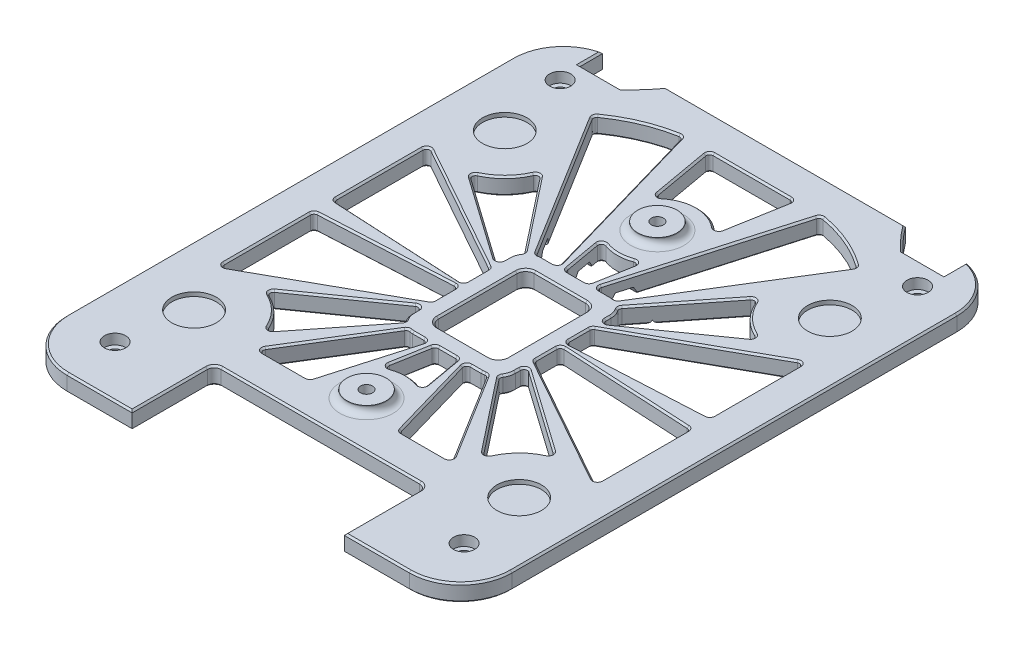
SolidWorks part; units mm, degrees
ref_plane "Front Plane" through (0, 0, 0) normal (0, 0, 1) x (1, 0, 0)
ref_plane "Top Plane" through (0, 0, 0) normal (0, 1, 0) x (1, 0, 0)
ref_plane "Right Plane" through (0, 0, 0) normal (1, 0, 0) x (0, 0, -1)
sketch "Sketch1" plane through (0, 0, 0) normal (0, 1, 0) x (1, 0, 0)
  line L0 (65, 160) -> (65, 24) construction
  line L5 (96, 0) -> (96, 22)
  line L7 (11.8, 153.04) -> (23.8, 153.04)
  line L9 (11.8, 153.04) -> (11.8, 159.6547)
  line L10 (118.2, 153.04) -> (106.2, 153.04)
  line L11 (118.2, 153.04) -> (118.2, 159.6547)
  line L18 (18, 160) -> (18, 155.5)
  line L19 (16.5, 154) -> (12.5, 154)
  line L20 (11, 155.5) -> (11, 159.4568)
  line L21 (0, 145) -> (0, 15)
  line L22 (15, 0) -> (34, 0)
  line L23 (34, 0) -> (34, 22.5)
  line L24 (35.5, 24) -> (90.5, 24)
  line L25 (96, 18.5) -> (96, 0)
  line L26 (96, 0) -> (115, 0)
  line L27 (130, 15) -> (130, 145)
  line L28 (119, 159.4568) -> (119, 155.5)
  line L29 (117.5, 154) -> (113.5, 154)
  line L30 (112, 155.5) -> (112, 160)
  line L31 (112, 160) -> (18, 160)
  line L35 (0, 145) -> (0, 15)
  line L36 (15, 0) -> (34, 0)
  line L37 (34, 0) -> (34, 22)
  line L38 (36, 24) -> (94, 24)
  line L40 (96, 0) -> (115, 0)
  line L41 (130, 15) -> (130, 145)
  line L45 (100, 160) -> (30, 160)
  circle A6 centre (116, 15) radius 1.75
  circle A7 centre (14, 15) radius 1.75
  circle A8 centre (65, 37.5) radius 1.75
  arc A10 (16.5, 154) -> (18, 155.5) centre (16.5, 155.5) ccw
  arc A11 (11, 155.5) -> (12.5, 154) centre (12.5, 155.5) ccw
  arc A12 (11, 159.4568) -> (0, 145) centre (15, 145) ccw
  arc A13 (0, 15) -> (15, 0) centre (15, 15) ccw
  arc A14 (35.5, 24) -> (34, 22.5) centre (35.5, 22.5) ccw
  arc A15 (96, 18.5) -> (90.5, 24) centre (90.5, 18.5) ccw
  arc A16 (115, 0) -> (130, 15) centre (115, 15) ccw
  arc A17 (130, 145) -> (119, 159.4568) centre (115, 145) ccw
  arc A18 (117.5, 154) -> (119, 155.5) centre (117.5, 155.5) ccw
  arc A19 (112, 155.5) -> (113.5, 154) centre (113.5, 155.5) ccw
  arc A22 (11, 159.4568) -> (0, 145) centre (15, 145) ccw
  arc A23 (0, 15) -> (15, 0) centre (15, 15) ccw
  arc A26 (115, 0) -> (130, 15) centre (115, 15) ccw
  arc A27 (130, 145) -> (119, 159.4568) centre (115, 145) ccw
  circle A30 centre (65, 122.5) radius 1.75
  circle A31 centre (12.78, 146.3) radius 1.75
  circle A32 centre (117.22, 146.3) radius 1.75
  arc A33 (36, 24) -> (34, 22) centre (36, 22) ccw
  arc A34 (94, 24) -> (96, 22) centre (94, 22) cw
  arc A35 (11, 159.4568) -> (11.8, 159.6547) centre (15, 145) cw
  arc A36 (23.8, 153.04) -> (30, 160) centre (-10.2724, 189.6333) ccw
  arc A37 (106.2, 153.04) -> (100, 160) centre (140.2724, 189.6333) cw
  arc A38 (119, 159.4568) -> (118.2, 159.6547) centre (115, 145) ccw
  dimension "D4" = 3.5
  dimension "D5" = 4
  dimension "D8" = 50
  dimension "D11" = 37.5
  dimension "D12" = 37.5
  dimension "D13" = 3.5
  dimension "D14" = 3.5
  dimension "D19" = 3.5
  dimension "D20" = 3.5
  dimension "D21" = 3.5
  dimension "D2" = 13.7
  dimension "D3" = 12.78
  dimension "D6" = 11.8
  dimension "D7" = 6.74
  dimension "D9" = 12
  dimension "D10" = 35
  dimension "D15" = 15
  dimension "D16" = 15
  dimension "D17" = 102
  dimension "D18" = 51
  dimension "D1" = 0
extrude "Boss-Extrude1" add sketch "Sketch1" along normal blind 5
chamfer "Chamfer1" distance 3.55 angle 45 2 edges at (65, 0, -35.75) (65, 0, -120.75)
sketch "Sketch2" plane through (0, 5, 0) normal (0, 1, 0) x (1, 0, 0)
  line L26 (15, 145) -> (15, 15)
  line L27 (15, 138.04) -> (15, 39) construction
  line L29 (100, 145) -> (36.9808, 145)
  line L30 (93.0192, 145) -> (36.9808, 145) construction
  line L40 (29.264, 138.04) -> (11.8, 138.04)
  line L41 (118.2, 138.04) -> (100.736, 138.04)
  line L42 (115, 138.04) -> (100.736, 138.04) construction
  line L43 (29.264, 138.04) -> (15, 138.04) construction
  line L45 (115, 15) -> (115, 145)
  line L46 (115, 39) -> (115, 138.04) construction
  line L48 (94, 39) -> (36, 39)
  line L49 (115, 39) -> (15, 39) construction
  circle A2 centre (65, 122.5) radius 11.75
  circle A3 centre (65, 122.5) radius 11.75 construction
  circle A5 centre (65, 37.5) radius 11.75
  circle A6 centre (65, 37.5) radius 11.75 construction
  arc A22 (34.0217, 142.062) -> (36.9808, 145) centre (-10.2724, 189.6333) ccw
  arc A28 (87.9183, 151.11) -> (100.736, 138.04) centre (140.2724, 189.6333) ccw
  arc A29 (93.0192, 145) -> (100.736, 138.04) centre (140.2724, 189.6333) ccw construction
  arc A30 (29.264, 138.04) -> (42.0817, 151.11) centre (-10.2724, 189.6333) ccw
  arc A31 (29.264, 138.04) -> (36.9808, 145) centre (-10.2724, 189.6333) ccw construction
  arc A33 (93.0192, 145) -> (76.6539, 39) centre (166.3728, 79.4116) ccw
  arc A34 (36.9808, 145) -> (53.3461, 39) centre (-36.3728, 79.4116) cw
  arc A35 (111, 22) -> (94, 39) centre (94, 22) ccw
  arc A36 (36, 39) -> (19, 22) centre (36, 22) ccw
  arc A41 (36.9808, 145) -> (53.3461, 39) centre (78.1854, 97.0983) ccw
  arc A42 (93.0192, 145) -> (76.6539, 39) centre (51.8146, 97.0983) cw
  dimension "D1" = 10
  dimension "D2" = 10
  dimension "D3" = 15
  dimension "D4" = 15
  dimension "D5" = 15
  dimension "D6" = 15
  dimension "D7" = 15
  dimension "D8" = 15
extrude "Cut-Extrude1" [suppressed] cut sketch "Sketch2" against normal up to next
sketch "Sketch5" plane through (0, 5, 0) normal (0, 1, 0) x (1, 0, 0)
  line L0 (65, 24) -> (65, 160) construction
  line L1 (36, 24) -> (94, 24) construction
  line L2 (100, 160) -> (30, 160) construction
  line L3 (0, 80) -> (130, 80) construction
  line L4 (0, 145) -> (0, 15) construction
  line L5 (130, 15) -> (130, 145) construction
  circle A0 centre (17.5, 34.6) radius 6.5
  circle A1 centre (65, 37.5) radius 1.75 construction
  circle A2 centre (65, 122.5) radius 1.75 construction
  circle A3 centre (17.5, 125.4) radius 6.5
  circle A4 centre (112.5, 34.6) radius 6.5
  circle A5 centre (112.5, 125.4) radius 6.5
  dimension "D1" = 13
  dimension "D3" = 2.9
  dimension "D4" = 42.5
  dimension "D2" = 47.5
extrude "Cut-Extrude3" cut sketch "Sketch5" against normal blind 1.2
sketch "Sketch6" plane through (0, 5, 0) normal (0, 1, 0) x (1, 0, 0)
  line L0 (130, 15) -> (130, 145) construction
  line L1 (0, 80) -> (130, 80) construction
  line L2 (0, 145) -> (0, 15) construction
  line L3 (50, 99) -> (50, 61) construction
  line L4 (50, 61) -> (80, 61) construction
  line L5 (80, 99) -> (80, 61) construction
  line L6 (50, 99) -> (80, 99) construction
  line L7 (65, 80) -> (104.0126, 143.04) construction
  line L8 (65, 80) -> (96.8102, 120.293) construction
  line L9 (65, 80) -> (120, 110.7031) construction
  line L10 (65, 80) -> (107.2351, 109.7625) construction
  line L11 (65, 80) -> (85.1379, 150) construction
  line L12 (65, 80) -> (77.4055, 150) construction
  line L13 (65, 80) -> (120, 82.8824) construction
  line L14 (61.6328, 99) -> (68.3672, 99)
  line L15 (68.3672, 99) -> (70.7122, 112.2319)
  line L16 (77.4055, 150) -> (73.8929, 130.1798)
  line L17 (77.4055, 150) -> (52.5945, 150)
  line L23 (70.466, 99) -> (85.1379, 150)
  line L24 (65, 160) -> (65, 24) construction
  line L29 (100, 160) -> (30, 160) construction
  line L30 (36, 24) -> (94, 24) construction
  line L32 (55, 94) -> (75, 94) construction
  line L33 (55, 94) -> (55, 66) construction
  line L34 (55, 66) -> (75, 66) construction
  line L35 (75, 94) -> (75, 66) construction
  line L36 (10, 143.04) -> (10, 15)
  line L37 (15, 10) -> (24, 10)
  line L38 (24, 10) -> (24, 22)
  line L39 (36, 34) -> (94, 34)
  line L40 (106, 22) -> (106, 10)
  line L41 (106, 10) -> (115, 10)
  line L42 (120, 15) -> (120, 143.04)
  line L43 (120, 143.04) -> (102.4695, 143.04)
  line L44 (95.2258, 150) -> (34.7742, 150)
  line L45 (27.5305, 143.04) -> (10, 143.04)
  line L46 (10, 143.04) -> (10, 15) construction
  line L47 (15, 10) -> (24, 10) construction
  line L48 (24, 10) -> (24, 22) construction
  line L49 (36, 34) -> (94, 34) construction
  line L50 (106, 22) -> (106, 10) construction
  line L51 (106, 10) -> (115, 10) construction
  line L52 (120, 15) -> (120, 143.04) construction
  line L53 (120, 143.04) -> (102.4695, 143.04) construction
  line L54 (95.2258, 150) -> (34.7742, 150) construction
  line L55 (27.5305, 143.04) -> (10, 143.04) construction
  line L57 (80, 90.5703) -> (107.2351, 109.7625)
  line L58 (120, 110.7031) -> (120, 82.8824)
  line L59 (120, 82.8824) -> (80, 80.7861)
  line L60 (80, 80.7861) -> (80, 88.3736)
  line L61 (80, 88.3736) -> (120, 110.7031)
  line L64 (57.5, 94) -> (72.5, 94)
  line L65 (75, 68.5) -> (75, 91.5)
  line L66 (80, 90.5703) -> (80, 94)
  line L67 (96.8102, 120.293) -> (78.7041, 97.3585)
  line L68 (103.5218, 142.247) -> (76.5963, 98.7383)
  line L69 (70.466, 99) -> (75, 99)
  line L70 (57.5, 66) -> (72.5, 66)
  line L71 (80, 79.2139) -> (80, 71.6264)
  line L72 (120, 77.1176) -> (80, 79.2139)
  line L73 (120, 49.2969) -> (120, 77.1176)
  line L74 (80, 71.6264) -> (120, 49.2969)
  line L75 (96.8102, 39.707) -> (78.7041, 62.6415)
  line L76 (80, 69.4297) -> (107.2351, 50.2375)
  line L77 (80, 69.4297) -> (80, 66)
  line L78 (70.466, 61) -> (85.1379, 10) construction
  line L79 (70.466, 61) -> (75, 61)
  line L80 (103.5218, 17.753) -> (76.5963, 61.2617) construction
  line L81 (68.3672, 61) -> (70.7122, 47.7681)
  line L82 (61.6328, 61) -> (68.3672, 61)
  line L87 (78.2335, 34) -> (94, 34)
  line L88 (94, 34) -> (93.4673, 34)
  line L89 (70.466, 61) -> (78.2335, 34)
  line L90 (76.5963, 61.2617) -> (93.4673, 34)
  line L91 (61.6328, 61) -> (59.2878, 47.7681)
  line L92 (59.534, 61) -> (55, 61)
  line L93 (59.534, 61) -> (51.7665, 34)
  line L94 (51.7665, 34) -> (36, 34)
  line L95 (36, 34) -> (36.5327, 34)
  line L96 (53.4037, 61.2617) -> (36.5327, 34)
  line L97 (50, 69.4297) -> (22.7649, 50.2375)
  line L98 (50, 69.4297) -> (50, 66)
  line L99 (33.1898, 39.707) -> (51.2959, 62.6415)
  line L100 (10, 77.1176) -> (50, 79.2139)
  line L101 (10, 49.2969) -> (10, 77.1176)
  line L102 (50, 71.6264) -> (10, 49.2969)
  line L103 (50, 79.2139) -> (50, 71.6264)
  line L104 (50, 80.7861) -> (50, 88.3736)
  line L105 (10, 82.8824) -> (50, 80.7861)
  line L106 (10, 110.7031) -> (10, 82.8824)
  line L107 (50, 88.3736) -> (10, 110.7031)
  line L108 (33.1898, 120.293) -> (51.2959, 97.3585)
  line L109 (50, 90.5703) -> (22.7649, 109.7625)
  line L110 (50, 90.5703) -> (50, 94)
  line L111 (59.534, 99) -> (44.8621, 150)
  line L112 (59.534, 99) -> (55, 99)
  line L113 (26.4782, 142.247) -> (53.4037, 98.7383)
  line L114 (61.6328, 99) -> (59.2878, 112.2319)
  line L115 (52.5945, 150) -> (56.1071, 130.1798)
  line L116 (55, 68.5) -> (55, 91.5)
  arc A0 (55, 61) -> (53.4037, 61.2617) centre (55, 66) cw
  arc A1 (96.8102, 120.293) -> (107.2351, 109.7625) centre (112.5, 125.4) ccw
  arc A2 (59.2878, 112.2319) -> (70.7122, 112.2319) centre (65, 122.5) ccw
  arc A3 (73.8929, 130.1798) -> (56.1071, 130.1798) centre (65, 122.5) ccw
  circle A4 centre (72.5, 91.5) radius 2.5 construction
  arc A5 (72.5, 94) -> (75, 91.5) centre (72.5, 91.5) cw
  circle A6 centre (75, 94) radius 5 construction
  arc A7 (78.7041, 97.3585) -> (80, 94) centre (75, 94) cw
  arc A8 (75, 99) -> (76.5963, 98.7383) centre (75, 94) cw
  arc A9 (85.1379, 150) -> (120, 110.7031) centre (78.7771, 109.2447) cw construction
  arc A10 (85.1379, 150) -> (103.5218, 142.247) centre (78.7771, 109.2447) cw
  arc A11 (72.5, 66) -> (75, 68.5) centre (72.5, 68.5) ccw
  arc A12 (96.8102, 39.707) -> (107.2351, 50.2375) centre (112.5, 34.6) cw
  arc A13 (78.7041, 62.6415) -> (80, 66) centre (75, 66) ccw
  arc A14 (75, 61) -> (76.5963, 61.2617) centre (75, 66) ccw
  arc A15 (85.1379, 10) -> (103.5218, 17.753) centre (78.7771, 50.7553) ccw construction
  arc A16 (59.2878, 47.7681) -> (70.7122, 47.7681) centre (65, 37.5) cw
  arc A18 (33.1898, 39.707) -> (22.7649, 50.2375) centre (17.5, 34.6) ccw
  arc A19 (51.2959, 62.6415) -> (50, 66) centre (55, 66) cw
  arc A20 (33.1898, 120.293) -> (22.7649, 109.7625) centre (17.5, 125.4) cw
  arc A21 (51.2959, 97.3585) -> (50, 94) centre (55, 94) ccw
  arc A22 (55, 99) -> (53.4037, 98.7383) centre (55, 94) ccw
  arc A23 (44.8621, 150) -> (26.4782, 142.247) centre (51.2229, 109.2447) ccw
  arc A24 (57.5, 66) -> (55, 68.5) centre (57.5, 68.5) cw
  arc A25 (57.5, 94) -> (55, 91.5) centre (57.5, 91.5) ccw
  circle A30 centre (17.5, 125.4) radius 16.5
  circle A31 centre (17.5, 125.4) radius 16.5 construction
  circle A33 centre (17.5, 34.6) radius 16.5
  circle A34 centre (17.5, 34.6) radius 16.5 construction
  circle A36 centre (112.5, 125.4) radius 16.5
  circle A37 centre (112.5, 125.4) radius 16.5 construction
  circle A39 centre (112.5, 34.6) radius 16.5
  circle A40 centre (112.5, 34.6) radius 16.5 construction
  circle A50 centre (65, 122.5) radius 11.75
  circle A51 centre (65, 122.5) radius 11.75 construction
  circle A53 centre (65, 37.5) radius 11.75
  circle A54 centre (65, 37.5) radius 11.75 construction
  arc A56 (10, 15) -> (15, 10) centre (15, 15) ccw
  arc A57 (36, 34) -> (24, 22) centre (36, 22) ccw
  arc A58 (106, 22) -> (94, 34) centre (94, 22) ccw
  arc A59 (115, 10) -> (120, 15) centre (115, 15) ccw
  arc A60 (95.2258, 150) -> (102.4695, 143.04) centre (140.2724, 189.6333) ccw
  arc A61 (27.5305, 143.04) -> (34.7742, 150) centre (-10.2724, 189.6333) ccw
  arc A62 (10, 15) -> (15, 10) centre (15, 15) ccw construction
  arc A63 (36, 34) -> (24, 22) centre (36, 22) ccw construction
  arc A64 (106, 22) -> (94, 34) centre (94, 22) ccw construction
  arc A65 (115, 10) -> (120, 15) centre (115, 15) ccw construction
  arc A66 (95.2258, 150) -> (102.4695, 143.04) centre (140.2724, 189.6333) ccw construction
  arc A67 (27.5305, 143.04) -> (34.7742, 150) centre (-10.2724, 189.6333) ccw construction
  point P26 (65, 94)
  point P38 (75, 80)
  point P104 (75, 80)
  point P163 (65, 66)
  point P168 (65, 94)
  dimension "D14" = 5
  dimension "D16" = 10
  dimension "D17" = 41.2487
  dimension "D8" = 55
  dimension "D10" = 14
  dimension "D12" = 3
  dimension "D13" = 6
  dimension "D15" = 6
  dimension "D1" = 10
  dimension "D2" = 10
  dimension "D3" = 10
  dimension "D4" = 10
  dimension "D5" = 10
  dimension "D6" = 10
  dimension "D7" = 10
extrude "Cut-Extrude4" cut sketch "Sketch6" against normal up to next contours L92 A0 L96 L94 L93 | A14 L79 L89 L87 L90 | L103 L100 L101 L102 | L99 A19 L98 L97 A18 | L104 L107 L106 L105 | A21 L108 A20 L109 L110 | L111 A23 L113 A22 L112 | A3 L16 L17 L115 | A10 L23 L69 A8 L68 | L67 A7 L66 L57 A1 | L61 L60 L59 L58 | L71 L74 L73 L72 | A13 L75 A12 L76 L77 | L91 A16 L81 L82 | L64 A25 L116 A24 L70 A11 L65 A5 | L114 A2 L15 L14
sketch "Sketch7" plane through (0, 5, 0) normal (0, 1, 0) x (1, 0, 0)
  circle A0 centre (65, 37.5) radius 5.75
  circle A1 centre (65, 122.5) radius 5.75
  circle A2 centre (65, 122.5) radius 1.75 construction
  circle A3 centre (65, 37.5) radius 1.75 construction
  circle A4 centre (65, 122.5) radius 1.75
  circle A5 centre (65, 37.5) radius 1.75
  dimension "D1" = 11.5
  dimension "D2" = 11.5
extrude "Boss-Extrude2" add sketch "Sketch7" along normal blind 2.2
fillet "Fillet1" radius 2 2 edges at (65, 5, -128.25) (65, 5, -43.25)
sketch "Sketch8" plane through (0, 5, 0) normal (0, 1, 0) x (1, 0, 0)
  circle A0 centre (12.78, 146.3) radius 3.1
  circle A1 centre (14, 15) radius 3.1
  circle A2 centre (117.22, 146.3) radius 3.1
  circle A3 centre (116, 15) radius 3.1
  dimension "D1" = 6.2
  dimension "D2" = 6.2
  dimension "D3" = 6.2
  dimension "D4" = 6.2
extrude "Cut-Extrude5" cut sketch "Sketch8" against normal blind 3
sketch "Sketch3" plane through (0, 0, 0) normal (0, -1, 0) x (1, 0, 0)
  text T0 "<b>gen3.0.1</b>" font "Century Gothic" height 4.5
extrude "Cut-Extrude2" cut sketch "Sketch3" against normal blind 0.5
fillet "Fillet2" radius 1 60 edges at (56.1071, 2.5, -130.1798) (73.8929, 2.5, -130.1798) (103.5218, 2.5, -142.247) (76.5963, 2.5, -98.7383) (78.7041, 2.5, -97.3585) (107.2351, 2.5, -109.7625) (80, 2.5, -80.7861) (120, 2.5, -82.8824) (120, 2.5, -49.2969) (80, 2.5, -69.4297) (78.7041, 2.5, -62.6415) (107.2351, 2.5, -50.2375) (93.4673, 2.5, -34) (70.7122, 2.5, -47.7681) (59.2878, 2.5, -47.7681) (22.7649, 2.5, -50.2375) (96.8102, 2.5, -39.707) (78.2335, 2.5, -34) (33.1898, 2.5, -39.707) (51.2959, 2.5, -62.6415) (10, 2.5, -49.2969) (50, 2.5, -90.5703) (51.2959, 2.5, -97.3585) (33.1898, 2.5, -120.293) (80, 2.5, -71.6264) (80, 2.5, -90.5703) (53.4037, 2.5, -98.7383) (61.6328, 2.5, -99) (70.466, 2.5, -99) (68.3672, 2.5, -99) (59.534, 2.5, -99) (50, 2.5, -71.6264) (50, 2.5, -80.7861) (10, 2.5, -82.8824) (22.7649, 2.5, -109.7625) (53.4037, 2.5, -61.2617) (61.6328, 2.5, -61) (70.466, 2.5, -61) (80, 2.5, -79.2139) (80, 2.5, -88.3736) (10, 2.5, -77.1176) (10, 2.5, -110.7031) (26.4782, 2.5, -142.247) (59.2878, 2.5, -112.2319) (85.1379, 2.5, -150) (52.5945, 2.5, -150) (120, 2.5, -77.1176) (76.5963, 2.5, -61.2617) (68.3672, 2.5, -61) (59.534, 2.5, -61) (50, 2.5, -69.4297) (50, 2.5, -88.3736) (50, 2.5, -79.2139) (96.8102, 2.5, -120.293) (120, 2.5, -110.7031) (70.7122, 2.5, -112.2319) (77.4055, 2.5, -150) (44.8621, 2.5, -150) (51.7665, 2.5, -34) (36.5327, 2.5, -34)
sketch "Sketch9" plane through (0, 0, 0) normal (0, -1, 0) x (1, 0, 0)
  line L0 (100, -160) -> (30, -160) construction
  line L1 (82.5, -107.5) -> (47.5, -107.5)
  line L2 (82.5, -107.5) -> (82.5, -103.5)
  line L3 (82.5, -103.5) -> (47.5, -103.5)
  line L4 (47.5, -107.5) -> (47.5, -103.5)
  line L5 (130, -15) -> (130, -145) construction
  dimension "D1" = 4
  dimension "D2" = 35
  dimension "D3" = 52.5
  dimension "D4" = 47.5
extrude "Cut-Extrude6" cut sketch "Sketch9" against normal blind 2
chamfer "Chamfer2" distance 1.2 angle 60 8 edges at (48.9785, 0, -103.5) (47.5, 0, -105.5) (81.0215, 0, -103.5) (82.5, 0, -105.5) (70.4626, 0, -103.5) (59.5374, 0, -103.5) (58.6076, 0, -107.5) (71.3924, 0, -107.5) first distance on face at (65, 0, -111.6729)
chamfer "Chamfer3" distance 0.5 angle 45 40 edges at (0, 5, -80) (4.3934, 5, -4.3934) (24.5, 5, 0) (34, 5, -11) (34.5858, 5, -23.4142) (65, 5, -24) (95.4142, 5, -23.4142) (96, 5, -11) (105.5, 5, 0) (125.6066, 5, -4.3934) (130, 5, -80) (126.6833, 5, -154.4074) (118.2, 5, -156.3473) (112.2, 5, -153.04) (102.9375, 5, -156.3752) (65, 5, -160) (27.0625, 5, -156.3752) (17.8, 5, -153.04) (11.8, 5, -156.3473) (3.3167, 5, -154.4074) (118.2, 0, -156.3473) (112.2, 0, -153.04) (102.9375, 0, -156.3752) (126.6833, 0, -154.4074) (130, 0, -80) (125.6066, 0, -4.3934) (105.5, 0, 0) (96, 0, -11) (95.4142, 0, -23.4142) (65, 0, -24) (34.5858, 0, -23.4142) (34, 0, -11) (24.5, 0, 0) (4.3934, 0, -4.3934) (0, 0, -80) (3.3167, 0, -154.4074) (11.8, 0, -156.3473) (17.8, 0, -153.04) (27.0625, 0, -156.3752) (65, 0, -160)
chamfer "Chamfer4" distance 0.5 angle 45 284 edges at (75, 5, -80) (74.2678, 5, -93.2678) (74.2678, 5, -66.7322) (65, 5, -94) (65, 5, -66) (55.7322, 5, -93.2678) (55.7322, 5, -66.7322) (55, 5, -80) (69.4467, 5, -54.9087) (68.1713, 5, -60.7663) (70.0373, 5, -48.7018) (65, 5, -61) (65, 5, -49.25) (61.8287, 5, -60.7663) (59.9627, 5, -48.7018) (60.5533, 5, -54.9087) (59.0047, 5, -60.6015) (55.5707, 5, -47.2235) (56.6029, 5, -61) (51.6151, 5, -34.2011) (54.5253, 5, -61.0226) (85.3294, 5, -34) (44.6706, 5, -34) (53.4643, 5, -61.024) (37.454, 5, -34.5133) (45.2464, 5, -48.0803) (51.0245, 5, -62.6082) (42.5439, 5, -51.5556) (50.2183, 5, -64.5386) (33.3681, 5, -40.7126) (50, 5, -66.7508) (29.2561, 5, -46.1777) (49.4604, 5, -68.3893) (23.8526, 5, -50.3922) (36.3482, 5, -59.8094) (30.4874, 5, -60.7338) (49.8624, 5, -71.7072) (10.4938, 5, -50.1381) (50, 5, -75.1868) (10, 5, -63.5845) (49.6884, 5, -78.8855) (10.2746, 5, -76.857) (29.9477, 5, -78.163) (29.9477, 5, -81.837) (49.6884, 5, -81.1145) (10.2746, 5, -83.143) (50, 5, -84.8132) (10, 5, -96.4155) (49.8624, 5, -88.2928) (10.4938, 5, -109.8619) (30.4874, 5, -99.2662) (49.4604, 5, -91.6107) (36.3482, 5, -100.1906) (50, 5, -93.2492) (23.8526, 5, -109.6078) (50.2183, 5, -95.4614) (29.2561, 5, -113.8223) (51.0245, 5, -97.3918) (33.3681, 5, -119.2874) (42.5439, 5, -108.4444) (53.4643, 5, -98.976) (39.9902, 5, -120.413) (54.5253, 5, -98.9774) (26.8348, 5, -142.1834) (56.6029, 5, -99) (35.2099, 5, -147.2583) (59.0047, 5, -99.3985) (44.6763, 5, -149.7155) (52.1377, 5, -124.7098) (54.2888, 5, -140.4401) (56.42, 5, -131.2885) (53.021, 5, -149.6425) (65, 5, -134.25) (65, 5, -150) (73.58, 5, -131.2885) (76.979, 5, -149.6425) (75.7112, 5, -140.4401) (60.5533, 5, -105.0913) (61.8287, 5, -99.2337) (59.9627, 5, -111.2982) (65, 5, -99) (65, 5, -110.75) (68.1713, 5, -99.2337) (70.0373, 5, -111.2982) (69.4467, 5, -105.0913) (70.9953, 5, -99.3985) (77.8623, 5, -124.7098) (73.3971, 5, -99) (85.3237, 5, -149.7155) (75.4747, 5, -98.9774) (94.7901, 5, -147.2583) (76.5357, 5, -98.976) (103.1652, 5, -142.1834) (90.0098, 5, -120.413) (78.9755, 5, -97.3918) (87.4561, 5, -108.4444) (79.7817, 5, -95.4614) (96.6319, 5, -119.2874) (80, 5, -93.2492) (100.7439, 5, -113.8223) (80.5396, 5, -91.6107) (106.1474, 5, -109.6078) (93.6518, 5, -100.1906) (99.5126, 5, -99.2662) (80.1376, 5, -88.2928) (119.5062, 5, -109.8619) (80, 5, -84.8132) (120, 5, -96.4155) (80.3116, 5, -81.1145) (119.7254, 5, -83.143) (100.0523, 5, -81.837) (100.0523, 5, -78.163) (80.3116, 5, -78.8855) (119.7254, 5, -76.857) (80, 5, -75.1868) (120, 5, -63.5845) (80.1376, 5, -71.7072) (119.5062, 5, -50.1381) (99.5126, 5, -60.7338) (80.5396, 5, -68.3893) (93.6518, 5, -59.8094) (80, 5, -66.7508) (106.1474, 5, -50.3922) (79.7817, 5, -64.5386) (100.7439, 5, -46.1777) (78.9755, 5, -62.6082) (96.6319, 5, -40.7126) (87.4561, 5, -51.5556) (76.5357, 5, -61.024) (84.7536, 5, -48.0803) (75.4747, 5, -61.0226) (92.546, 5, -34.5133) (73.3971, 5, -61) (70.9953, 5, -60.6015) (78.3849, 5, -34.2011) (74.4293, 5, -47.2235) (75, 0, -80) (74.2678, 0, -93.2678) (74.2678, 0, -66.7322) (65, 0, -94) (65, 0, -66) (55.7322, 0, -93.2678) (55.7322, 0, -66.7322) (55, 0, -80) (12.78, 0, -144.55) (117.22, 0, -148.05) (116, 0, -13.25) (14, 0, -13.25) (60.5533, 0, -54.9087) (59.9627, 0, -48.7018) (61.8287, 0, -60.7663) (65, 0, -49.25) (65, 0, -61) (70.0373, 0, -48.7018) (68.1713, 0, -60.7663) (69.4467, 0, -54.9087) (74.4293, 0, -47.2235) (70.9953, 0, -60.6015) (78.3849, 0, -34.2011) (73.3971, 0, -61) (85.3294, 0, -34) (75.4747, 0, -61.0226) (92.546, 0, -34.5133) (76.5357, 0, -61.024) (84.7536, 0, -48.0803) (87.4561, 0, -51.5556) (78.9755, 0, -62.6082) (96.6319, 0, -40.7126) (79.7817, 0, -64.5386) (100.7439, 0, -46.1777) (80, 0, -66.7508) (106.1474, 0, -50.3922) (80.5396, 0, -68.3893) (93.6518, 0, -59.8094) (99.5126, 0, -60.7338) (119.5062, 0, -50.1381) (80.1376, 0, -71.7072) (120, 0, -63.5845) (80, 0, -75.1868) (119.7254, 0, -76.857) (80.3116, 0, -78.8855) (100.0523, 0, -78.163) (100.0523, 0, -81.837) (119.7254, 0, -83.143) (80.3116, 0, -81.1145) (120, 0, -96.4155) (80, 0, -84.8132) (119.5062, 0, -109.8619) (80.1376, 0, -88.2928) (99.5126, 0, -99.2662) (93.6518, 0, -100.1906) (80.8976, 0, -100.137) (78.9755, 0, -97.3918) (79.7817, 0, -95.4614) (80, 0, -93.2492) (80.5396, 0, -91.6107) (106.1474, 0, -109.6078) (100.7439, 0, -113.8223) (96.6319, 0, -119.2874) (89.7111, 0, -111.3008) (92.5268, 0, -124.4802) (77.8925, 0, -100.8328) (71.1243, 0, -101.2882) (76.5357, 0, -98.976) (70.9953, 0, -99.3985) (75.4747, 0, -98.9774) (73.3971, 0, -99) (70.2331, 0, -109.5285) (59.7669, 0, -109.5285) (70.0373, 0, -111.2982) (59.9627, 0, -111.2982) (65, 0, -110.75) (61.2672, 0, -101.0627) (68.7328, 0, -101.0627) (61.8287, 0, -99.2337) (68.1713, 0, -99.2337) (65, 0, -99) (52.1075, 0, -100.8328) (53.4643, 0, -98.976) (58.8757, 0, -101.2882) (54.5253, 0, -98.9774) (59.0047, 0, -99.3985) (56.6029, 0, -99) (103.1652, 0, -142.1834) (94.7901, 0, -147.2583) (85.3237, 0, -149.7155) (79.0739, 0, -128.9215) (75.7112, 0, -140.4401) (76.979, 0, -149.6425) (73.58, 0, -131.2885) (65, 0, -150) (65, 0, -134.25) (53.021, 0, -149.6425) (56.42, 0, -131.2885) (54.2888, 0, -140.4401) (50.9261, 0, -128.9215) (44.6763, 0, -149.7155) (35.2099, 0, -147.2583) (26.8348, 0, -142.1834) (37.4732, 0, -124.4802) (49.1024, 0, -100.137) (40.2889, 0, -111.3008) (51.0245, 0, -97.3918) (33.3681, 0, -119.2874) (50.2183, 0, -95.4614) (29.2561, 0, -113.8223) (50, 0, -93.2492) (23.8526, 0, -109.6078) (49.4604, 0, -91.6107) (36.3482, 0, -100.1906) (30.4874, 0, -99.2662) (10.4938, 0, -109.8619) (49.8624, 0, -88.2928) (10, 0, -96.4155) (50, 0, -84.8132) (10.2746, 0, -83.143) (49.6884, 0, -81.1145) (29.9477, 0, -81.837) (29.9477, 0, -78.163) (10.2746, 0, -76.857) (49.6884, 0, -78.8855) (10, 0, -63.5845) (50, 0, -75.1868) (10.4938, 0, -50.1381) (49.8624, 0, -71.7072) (30.4874, 0, -60.7338) (36.3482, 0, -59.8094) (49.4604, 0, -68.3893) (23.8526, 0, -50.3922) (50, 0, -66.7508) (29.2561, 0, -46.1777) (50.2183, 0, -64.5386) (33.3681, 0, -40.7126) (51.0245, 0, -62.6082) (42.5439, 0, -51.5556) (45.2464, 0, -48.0803) (53.4643, 0, -61.024) (37.454, 0, -34.5133) (54.5253, 0, -61.0226) (44.6706, 0, -34) (56.6029, 0, -61) (51.6151, 0, -34.2011) (59.0047, 0, -60.6015) (55.5707, 0, -47.2235)
